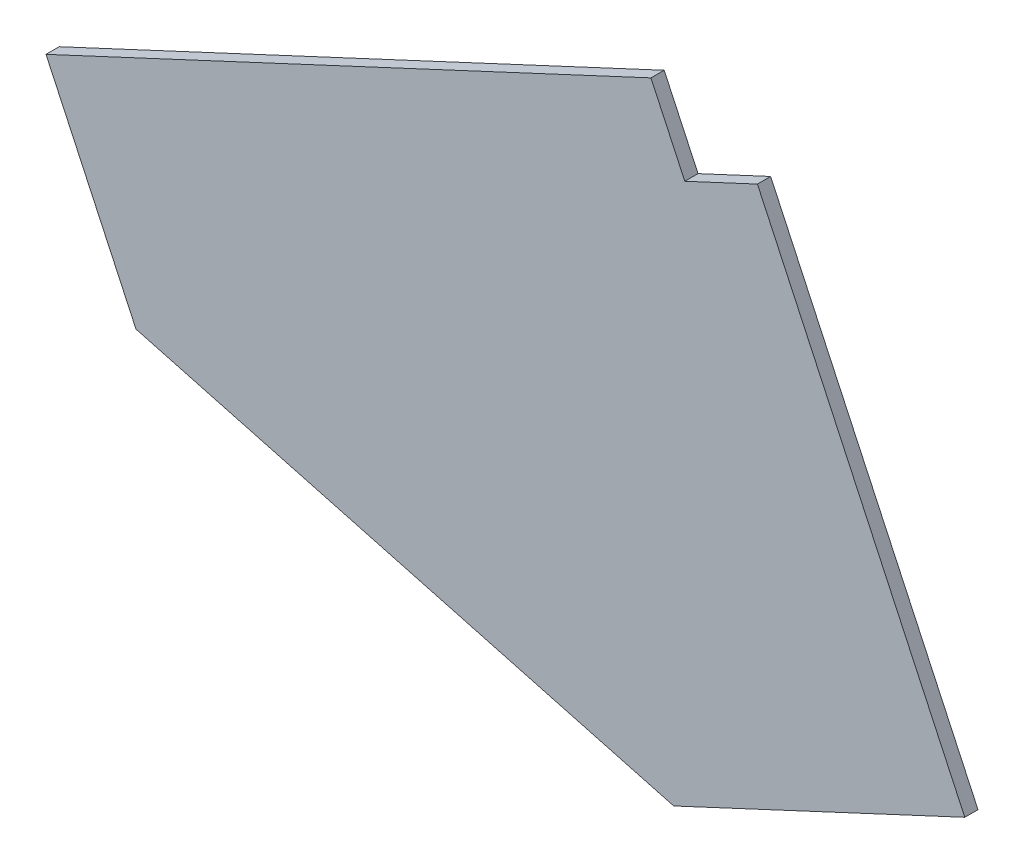
SolidWorks part; units mm, degrees
material "Balsa"
ref_plane "Front Plane" through (0, 0, 0) normal (0, 0, 1) x (1, 0, 0)
ref_plane "Top Plane" through (0, 0, 0) normal (0, 1, 0) x (1, 0, 0)
ref_plane "Right Plane" through (0, 0, 0) normal (1, 0, 0) x (0, 0, -1)
sketch "Sketch1" plane through (0, 0, 0) normal (0, 0, 1) x (1, 0, 0)
  line L0 (365.9798, -82.6535) -> (130.6366, -19.5934)
  line L1 (130.6366, -19.5934) -> (108.169, 28.5884)
  line L2 (108.169, 28.5884) -> (259.1989, 99.0148)
  line L3 (-63.4467, -51.4373) -> (255.5737, 97.3243) construction
  line L4 (259.1989, 99.0148) -> (267.6513, 80.8887)
  line L5 (267.6513, 80.8887) -> (285.7774, 89.341)
  line L6 (285.7774, 89.341) -> (365.9798, -82.6535)
  line L7 (327.4362, 0.0035) -> (398.701, -152.8244) construction
  line L10 (337.5482, -21.6817) -> (264.8848, -55.5651)
  line L12 (50.7481, 1.8126) -> (264.8848, -55.5651) construction
  line L15 (130.6366, -19.5934) -> (108.169, 28.5884) construction
  line L16 (309.1473, -45.959) -> (223.9543, -85.6851) construction
  dimension "D1" = 20
  dimension "D2" = 20
  dimension "D3" = 10
extrude "Boss-Extrude1" add sketch "Sketch1" against normal blind 3.3 contours L10 L6 L5 L4 L2 L1 L0 region at (229.671, 15.5188, 0)
